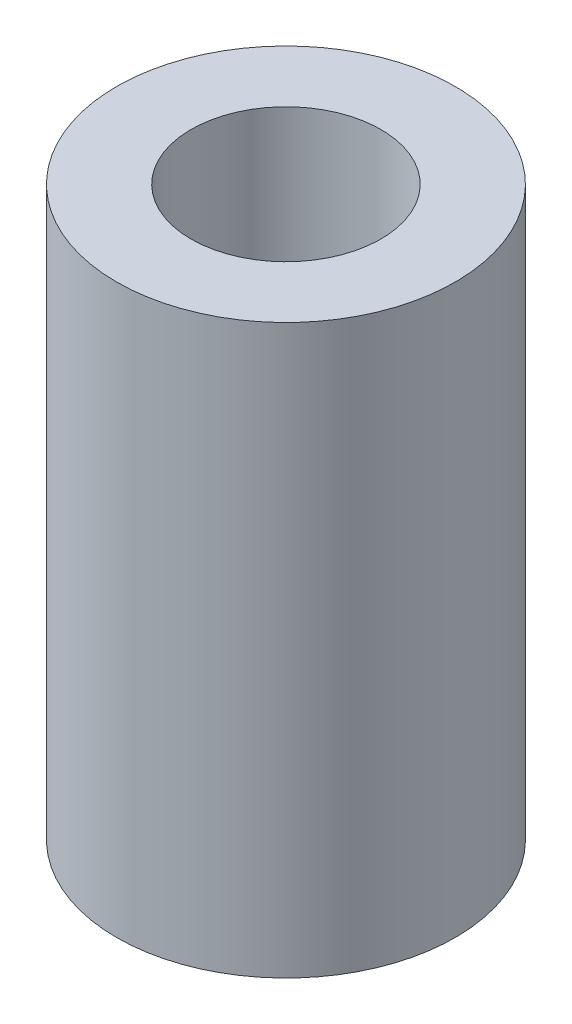
SolidWorks part; units mm, degrees
ref_plane "Front Plane" through (0, 0, 0) normal (0, 0, 1) x (1, 0, 0)
ref_plane "Top Plane" through (0, 0, 0) normal (0, 1, 0) x (1, 0, 0)
ref_plane "Right Plane" through (0, 0, 0) normal (1, 0, 0) x (0, 0, -1)
sketch "Sketch1" plane through (0, 0, 0) normal (0, 1, 0) x (1, 0, 0)
  circle A0 centre (0, 0) radius 7.5
  dimension "SLEEVE_OD" = 15
extrude "Boss-Extrude1" add sketch "Sketch1" along normal blind 25.1448
sketch "Sketch2" plane through (0, 0, 0) normal (0, 1, 0) x (1, 0, 0)
  circle A0 centre (0, 0) radius 4.2052
  dimension "BORE_D" = 8.4104
extrude "Cut-Extrude1" cut sketch "Sketch2" along normal through all
chamfer "Chamfer1" distance 1.4669 angle 56.246 rebuild error yes
